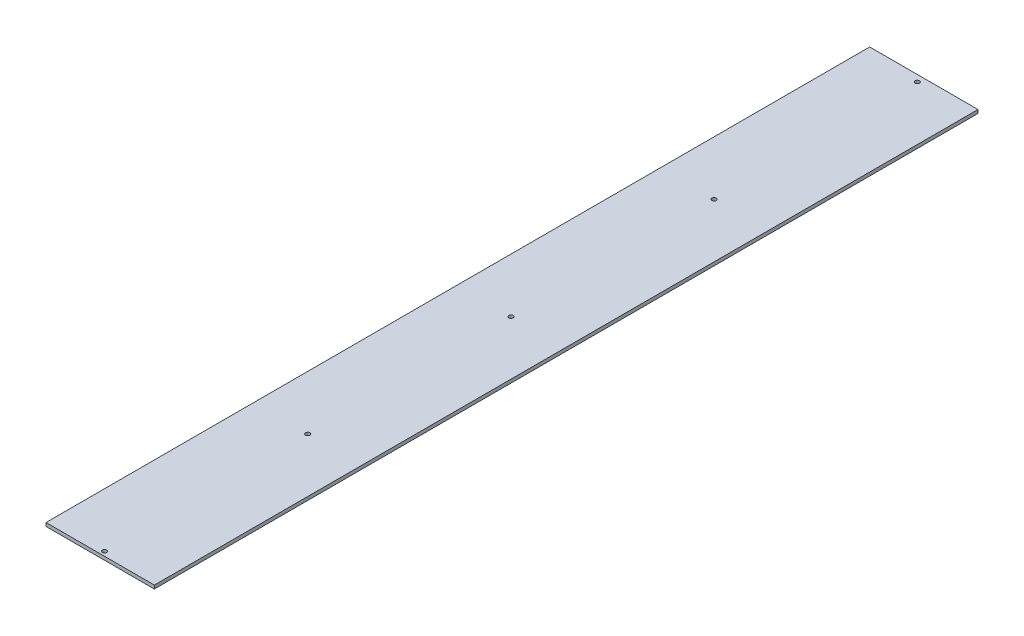
SolidWorks part; units mm, degrees
ref_plane "Front Plane" through (0, 0, 0) normal (0, 0, 1) x (1, 0, 0)
ref_plane "Top Plane" through (0, 0, 0) normal (0, 1, 0) x (1, 0, 0)
ref_plane "Right Plane" through (0, 0, 0) normal (1, 0, 0) x (0, 0, -1)
sketch "Sketch1" plane through (0, 0, 0) normal (0, 1, 0) x (1, 0, 0)
  line L0 (0, 190.075) -> (0, -190.075) construction
  line L1 (-25, -190.075) -> (25, -190.075)
  line L2 (-25, -190.075) -> (-25, 190.075)
  line L3 (-25, 190.075) -> (25, 190.075)
  line L4 (25, -190.075) -> (25, 190.075)
  line L5 (-25, -190.075) -> (25, 190.075) construction
  line L6 (-25, 190.075) -> (25, -190.075) construction
  point P0 (0, 0)
  dimension "D1" = 380.15
  dimension "D2" = 50
base flange "Base-Flange1" sketch "Sketch1" thickness 1.6 reverse thickness direction no parameters "D1"=0.6
sketch "Sketch6" plane through (0, 0, 0) normal (0, 1, 0) x (1, 0, 0)
  line L0 (0, 190.075) -> (0, -200.782) construction
  line L1 (25, 190.075) -> (-25, 190.075) construction
  circle A0 centre (0, 187.075) radius 1
  dimension "D2" = 2
  dimension "D1" = 3
extrude "Cut-Extrude1" cut sketch "Sketch6" against normal blind 10 normal cut yes
pattern_linear "LPattern1" count 5 spacing 93.7875 along (0, 0, 1) of "Cut-Extrude1"
sketch "Bend-Lines1" plane through (0, 0, 0) normal (0, 1, 0) x (1, 0, 0)
sketch "Bounding-Box1" plane through (0, 0, 0) normal (0, 1, 0) x (1, 0, 0)
sheet metal parameters "Sheet-Metal(1)" thickness 1.6 parameters "D1"=0.6
flat pattern "Flat-Pattern(1)" [suppressed]
sketch "Bend-Lines2" plane through (0, 0, 0) normal (0, 1, 0) x (1, 0, 0)
sketch "Bounding-Box2" [suppressed] plane through (0, 0, 0) normal (0, 1, 0) x (1, 0, 0)
sheet metal parameters "Sheet-Metal(2)" thickness 1.6 parameters "D1"=0.6
flat pattern "Flat-Pattern(1)"
sketch "Bend-Lines2" plane through (0, 0, 0) normal (0, 1, 0) x (1, 0, 0)
sketch "Bounding-Box2" [suppressed] plane through (0, 0, 0) normal (0, 1, 0) x (1, 0, 0)
sheet metal parameters "Sheet-Metal(3)" thickness 1.6 parameters "D1"=0.6
flat pattern "Flat-Pattern(1)"
sketch "Bend-Lines2" plane through (0, 0, 0) normal (0, 1, 0) x (1, 0, 0)
sketch "Bounding-Box2" [suppressed] plane through (0, 0, 0) normal (0, 1, 0) x (1, 0, 0)
